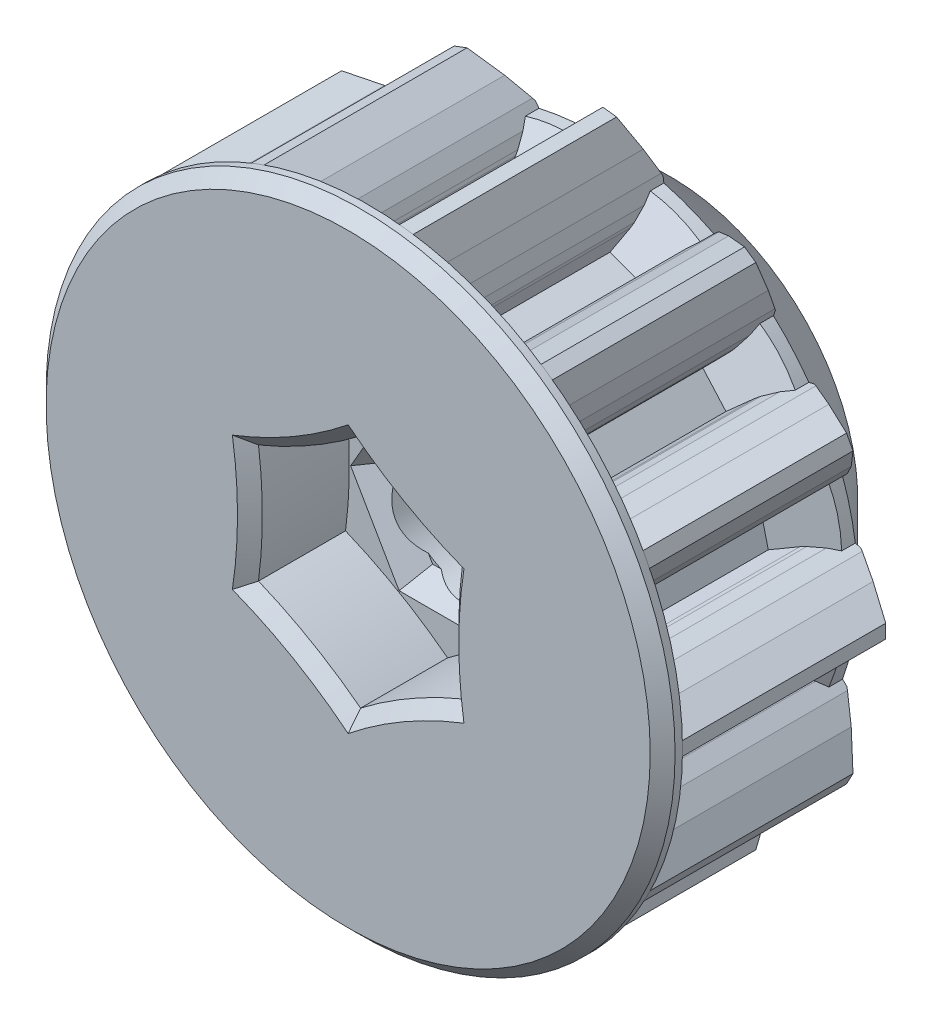
SolidWorks part; units mm, degrees
material "Custom Plastic"
ref_plane "Front Plane" through (0, 0, 0) normal (0, 0, 1) x (1, 0, 0)
ref_plane "Top Plane" through (0, 0, 0) normal (0, 1, 0) x (1, 0, 0)
ref_plane "Right Plane" through (0, 0, 0) normal (1, 0, 0) x (0, 0, -1)
sketch "Model" plane through (0, 0, 0) normal (0, 0, 1) x (1, 0, 0)
  line L0 (-12.322, -2.752) -> (-11.499, -1.837)
  line L1 (-11.499, -1.837) -> (-10.75, -1.243)
  line L2 (-10.75, -1.243) -> (-10.152, -0.913)
  line L3 (-10.152, -0.913) -> (-9.766, -0.777)
  line L4 (-9.766, -0.777) -> (-9.632, -0.751)
  line L5 (-9.632, -0.751) -> (-8.992, -0.701)
  line L6 (-8.992, -0.701) -> (-8.992, 0.701)
  line L7 (-8.992, 0.701) -> (-9.632, 0.751)
  line L8 (-9.632, 0.751) -> (-9.766, 0.777)
  line L9 (-9.766, 0.777) -> (-10.152, 0.913)
  line L10 (-10.152, 0.913) -> (-10.75, 1.243)
  line L11 (-10.75, 1.243) -> (-11.499, 1.837)
  line L12 (-11.499, 1.837) -> (-12.322, 2.752)
  line L13 (-12.322, 2.752) -> (-12.189, 3.29)
  line L14 (-12.189, 3.29) -> (-11.036, 3.717)
  line L15 (-11.036, 3.717) -> (-10.096, 3.895)
  line L16 (-10.096, 3.895) -> (-9.414, 3.91)
  line L17 (-9.414, 3.91) -> (-9.008, 3.851)
  line L18 (-9.008, 3.851) -> (-8.878, 3.811)
  line L19 (-8.878, 3.811) -> (-8.288, 3.558)
  line L20 (-8.288, 3.558) -> (-7.637, 4.8)
  line L21 (-7.637, 4.8) -> (-8.18, 5.141)
  line L22 (-8.18, 5.141) -> (-8.286, 5.226)
  line L23 (-8.286, 5.226) -> (-8.565, 5.527)
  line L24 (-8.565, 5.527) -> (-8.941, 6.096)
  line L25 (-8.941, 6.096) -> (-9.328, 6.971)
  line L26 (-9.328, 6.971) -> (-9.631, 8.163)
  line L27 (-9.631, 8.163) -> (-9.264, 8.577)
  line L28 (-9.264, 8.577) -> (-8.045, 8.42)
  line L29 (-8.045, 8.42) -> (-7.129, 8.141)
  line L30 (-7.129, 8.141) -> (-6.519, 7.837)
  line L31 (-6.519, 7.837) -> (-6.187, 7.596)
  line L32 (-6.187, 7.596) -> (-6.09, 7.501)
  line L33 (-6.09, 7.501) -> (-5.685, 7.002)
  line L34 (-5.685, 7.002) -> (-4.532, 7.799)
  line L35 (-4.532, 7.799) -> (-4.854, 8.354)
  line L36 (-4.854, 8.354) -> (-4.908, 8.478)
  line L37 (-4.908, 8.478) -> (-5.016, 8.874)
  line L38 (-5.016, 8.874) -> (-5.084, 9.553)
  line L39 (-5.084, 9.553) -> (-5.02, 10.508)
  line L40 (-5.02, 10.508) -> (-4.735, 11.704)
  line L41 (-4.735, 11.704) -> (-4.217, 11.9)
  line L42 (-4.217, 11.9) -> (-3.21, 11.194)
  line L43 (-3.21, 11.194) -> (-2.529, 10.522)
  line L44 (-2.529, 10.522) -> (-2.13, 9.968)
  line L45 (-2.13, 9.968) -> (-1.948, 9.601)
  line L46 (-1.948, 9.601) -> (-1.907, 9.471)
  line L47 (-1.907, 9.471) -> (-1.78, 8.842)
  line L48 (-1.78, 8.842) -> (-0.388, 9.011)
  line L49 (-0.388, 9.011) -> (-0.416, 9.652)
  line L50 (-0.416, 9.652) -> (-0.406, 9.788)
  line L51 (-0.406, 9.788) -> (-0.317, 10.189)
  line L52 (-0.317, 10.189) -> (-0.062, 10.821)
  line L53 (-0.062, 10.821) -> (0.438, 11.637)
  line L54 (0.438, 11.637) -> (1.246, 12.563)
  line L55 (1.246, 12.563) -> (1.796, 12.497)
  line L56 (1.796, 12.497) -> (2.36, 11.404)
  line L57 (2.36, 11.404) -> (2.65, 10.492)
  line L58 (2.65, 10.492) -> (2.746, 9.817)
  line L59 (2.746, 9.817) -> (2.737, 9.407)
  line L60 (2.737, 9.407) -> (2.713, 9.273)
  line L61 (2.713, 9.273) -> (2.533, 8.657)
  line L62 (2.533, 8.657) -> (3.845, 8.16)
  line L63 (3.845, 8.16) -> (4.118, 8.74)
  line L64 (4.118, 8.74) -> (4.189, 8.856)
  line L65 (4.189, 8.856) -> (4.454, 9.169)
  line L66 (4.454, 9.169) -> (4.974, 9.611)
  line L67 (4.974, 9.611) -> (5.796, 10.101)
  line L68 (5.796, 10.101) -> (6.942, 10.545)
  line L69 (6.942, 10.545) -> (7.398, 10.23)
  line L70 (7.398, 10.23) -> (7.389, 9.001)
  line L71 (7.389, 9.001) -> (7.222, 8.059)
  line L72 (7.222, 8.059) -> (6.994, 7.416)
  line L73 (6.994, 7.416) -> (6.795, 7.057)
  line L74 (6.795, 7.057) -> (6.712, 6.949)
  line L75 (6.712, 6.949) -> (6.266, 6.487)
  line L76 (6.266, 6.487) -> (7.196, 5.438)
  line L77 (7.196, 5.438) -> (7.708, 5.825)
  line L78 (7.708, 5.825) -> (7.825, 5.895)
  line L79 (7.825, 5.895) -> (8.205, 6.049)
  line L80 (8.205, 6.049) -> (8.871, 6.198)
  line L81 (8.871, 6.198) -> (9.826, 6.25)
  line L82 (9.826, 6.25) -> (11.047, 6.111)
  line L83 (11.047, 6.111) -> (11.305, 5.62)
  line L84 (11.305, 5.62) -> (10.726, 4.536)
  line L85 (10.726, 4.536) -> (10.14, 3.779)
  line L86 (10.14, 3.779) -> (9.639, 3.316)
  line L87 (9.639, 3.316) -> (9.296, 3.091)
  line L88 (9.296, 3.091) -> (9.173, 3.034)
  line L89 (9.173, 3.034) -> (8.563, 2.832)
  line L90 (8.563, 2.832) -> (8.899, 1.471)
  line L91 (8.899, 1.471) -> (9.532, 1.576)
  line L92 (9.532, 1.576) -> (9.668, 1.583)
  line L93 (9.668, 1.583) -> (10.076, 1.543)
  line L94 (10.076, 1.543) -> (10.735, 1.366)
  line L95 (10.735, 1.366) -> (11.605, 0.968)
  line L96 (11.605, 0.968) -> (12.622, 0.277)
  line L97 (12.622, 0.277) -> (12.622, -0.277)
  line L98 (12.622, -0.277) -> (11.605, -0.968)
  line L99 (11.605, -0.968) -> (10.735, -1.366)
  line L100 (10.735, -1.366) -> (10.076, -1.543)
  line L101 (10.076, -1.543) -> (9.668, -1.583)
  line L102 (9.668, -1.583) -> (9.532, -1.576)
  line L103 (9.532, -1.576) -> (8.899, -1.471)
  line L104 (8.899, -1.471) -> (8.563, -2.832)
  line L105 (8.563, -2.832) -> (9.173, -3.034)
  line L106 (9.173, -3.034) -> (9.296, -3.091)
  line L107 (9.296, -3.091) -> (9.639, -3.316)
  line L108 (9.639, -3.316) -> (10.14, -3.779)
  line L109 (10.14, -3.779) -> (10.726, -4.536)
  line L110 (10.726, -4.536) -> (11.305, -5.62)
  line L111 (11.305, -5.62) -> (11.047, -6.111)
  line L112 (11.047, -6.111) -> (9.826, -6.25)
  line L113 (9.826, -6.25) -> (8.871, -6.198)
  line L114 (8.871, -6.198) -> (8.205, -6.049)
  line L115 (8.205, -6.049) -> (7.825, -5.895)
  line L116 (7.825, -5.895) -> (7.708, -5.825)
  line L117 (7.708, -5.825) -> (7.196, -5.438)
  line L118 (7.196, -5.438) -> (6.266, -6.487)
  line L119 (6.266, -6.487) -> (6.712, -6.949)
  line L120 (6.712, -6.949) -> (6.795, -7.057)
  line L121 (6.795, -7.057) -> (6.994, -7.416)
  line L122 (6.994, -7.416) -> (7.222, -8.059)
  line L123 (7.222, -8.059) -> (7.389, -9.001)
  line L124 (7.389, -9.001) -> (7.398, -10.23)
  line L125 (7.398, -10.23) -> (6.942, -10.545)
  line L126 (6.942, -10.545) -> (5.796, -10.101)
  line L127 (5.796, -10.101) -> (4.974, -9.611)
  line L128 (4.974, -9.611) -> (4.454, -9.169)
  line L129 (4.454, -9.169) -> (4.189, -8.856)
  line L130 (4.189, -8.856) -> (4.118, -8.74)
  line L131 (4.118, -8.74) -> (3.845, -8.16)
  line L132 (3.845, -8.16) -> (2.533, -8.657)
  line L133 (2.533, -8.657) -> (2.713, -9.273)
  line L134 (2.713, -9.273) -> (2.737, -9.407)
  line L135 (2.737, -9.407) -> (2.746, -9.817)
  line L136 (2.746, -9.817) -> (2.65, -10.492)
  line L137 (2.65, -10.492) -> (2.36, -11.404)
  line L138 (2.36, -11.404) -> (1.796, -12.497)
  line L139 (1.796, -12.497) -> (1.246, -12.563)
  line L140 (1.246, -12.563) -> (0.438, -11.637)
  line L141 (0.438, -11.637) -> (-0.062, -10.821)
  line L142 (-0.062, -10.821) -> (-0.317, -10.189)
  line L143 (-0.317, -10.189) -> (-0.406, -9.788)
  line L144 (-0.406, -9.788) -> (-0.416, -9.652)
  line L145 (-0.416, -9.652) -> (-0.388, -9.011)
  line L146 (-0.388, -9.011) -> (-1.78, -8.842)
  line L147 (-1.78, -8.842) -> (-1.907, -9.471)
  line L148 (-1.907, -9.471) -> (-1.948, -9.601)
  line L149 (-1.948, -9.601) -> (-2.13, -9.968)
  line L150 (-2.13, -9.968) -> (-2.529, -10.522)
  line L151 (-2.529, -10.522) -> (-3.21, -11.194)
  line L152 (-3.21, -11.194) -> (-4.217, -11.9)
  line L153 (-4.217, -11.9) -> (-4.735, -11.704)
  line L154 (-4.735, -11.704) -> (-5.02, -10.508)
  line L155 (-5.02, -10.508) -> (-5.084, -9.553)
  line L156 (-5.084, -9.553) -> (-5.016, -8.874)
  line L157 (-5.016, -8.874) -> (-4.908, -8.478)
  line L158 (-4.908, -8.478) -> (-4.854, -8.354)
  line L159 (-4.854, -8.354) -> (-4.532, -7.799)
  line L160 (-4.532, -7.799) -> (-5.685, -7.002)
  line L161 (-5.685, -7.002) -> (-6.09, -7.501)
  line L162 (-6.09, -7.501) -> (-6.187, -7.596)
  line L163 (-6.187, -7.596) -> (-6.519, -7.837)
  line L164 (-6.519, -7.837) -> (-7.129, -8.141)
  line L165 (-7.129, -8.141) -> (-8.045, -8.42)
  line L166 (-8.045, -8.42) -> (-9.264, -8.577)
  line L167 (-9.264, -8.577) -> (-9.631, -8.163)
  line L168 (-9.631, -8.163) -> (-9.328, -6.971)
  line L169 (-9.328, -6.971) -> (-8.941, -6.096)
  line L170 (-8.941, -6.096) -> (-8.565, -5.527)
  line L171 (-8.565, -5.527) -> (-8.286, -5.226)
  line L172 (-8.286, -5.226) -> (-8.18, -5.141)
  line L173 (-8.18, -5.141) -> (-7.637, -4.8)
  line L174 (-7.637, -4.8) -> (-8.288, -3.558)
  line L175 (-8.288, -3.558) -> (-8.878, -3.811)
  line L176 (-8.878, -3.811) -> (-9.008, -3.851)
  line L177 (-9.008, -3.851) -> (-9.414, -3.91)
  line L178 (-9.414, -3.91) -> (-10.096, -3.895)
  line L179 (-10.096, -3.895) -> (-11.036, -3.717)
  line L180 (-11.036, -3.717) -> (-12.189, -3.29)
  line L181 (-12.189, -3.29) -> (-12.322, -2.752)
  line L182 (0, 0) -> (12.622, 0) construction
  line L183 (8.899, 1.471) -> (8.899, -1.471) construction
  line L184 (9.532, 1.576) -> (9.532, -1.576) construction
  line L185 (9.668, 1.583) -> (9.668, -1.583) construction
  line L186 (10.076, 1.543) -> (10.076, -1.543) construction
  line L187 (10.735, 1.366) -> (10.735, -1.366) construction
  line L188 (11.605, 0.968) -> (11.605, -0.968) construction
  circle A0 centre (0, 0) radius 1.5 construction
  dimension "D1" = 3
  dimension "D2" = 12.622
  dimension "D3" = 0.554
  dimension "D4" = 2.942
  dimension "D5" = 3.152
  dimension "D6" = 3.166
  dimension "D7" = 3.086
  dimension "D8" = 2.732
  dimension "D9" = 1.936
  dimension "D10" = 8.899
  dimension "D11" = 9.532
  dimension "D12" = 9.668
  dimension "D13" = 10.076
  dimension "D14" = 10.735
  dimension "D15" = 11.605
extrude "Boss-Extrude1" add sketch "Model" along normal blind 10
sketch "Sketch1" plane through (0, 0, 0) normal (0, 0, -1) x (-1, 0, 0)
  circle A0 centre (0, 0) radius 10.5
  dimension "D1" = 21
extrude "Boss-Extrude2" add sketch "Sketch1" along normal blind 3
sketch "Sketch6" plane through (0, 0, 10) normal (0, 0, 1) x (1, 0, 0)
  circle A0 centre (0, 0) radius 12.65
  dimension "D1" = 25.3
extrude "Boss-Extrude3" add sketch "Sketch6" against normal blind 0.8
chamfer "Chamfer1" distance 2 distance2 2 13 edges at (8.731, -2.1515, 0) (6.731, -5.9625, 0) (3.189, -8.4085, 0) (-1.084, -8.9265, 0) (-5.1085, -7.4005, 0) (-7.9625, -4.179, 0) (-8.992, 0, 0) (-7.9625, 4.179, 0) (-5.1085, 7.4005, 0) (-1.084, 8.9265, 0) (3.189, 8.4085, 0) (6.731, 5.9625, 0) (8.731, 2.1515, 0)
sketch "Sketch2" plane through (0, 0, 10) normal (0, 0, 1) x (1, 0, 0)
  circle A0 centre (0, 0) radius 3.05
  dimension "D1" = 6.1
extrude "Cut-Extrude1" cut sketch "Sketch2" against normal through all
sketch "Sketch3" plane through (0, 0, -3) normal (0, 0, -1) x (-1, 0, 0)
  circle A0 centre (0, 0) radius 5.05
  dimension "D1" = 10.1
extrude "Cut-Extrude2" cut sketch "Sketch3" against normal blind 4
sketch "Sketch4" plane through (0, 0, 10) normal (0, 0, 1) x (1, 0, 0)
  line L1 (3.9, 0) -> (1.95, 3.3775)
  line L2 (1.95, 3.3775) -> (-1.95, 3.3775)
  line L3 (-1.95, 3.3775) -> (-3.9, 0)
  line L4 (-3.9, 0) -> (-1.95, -3.3775)
  line L5 (-1.95, -3.3775) -> (1.95, -3.3775)
  line L6 (1.95, -3.3775) -> (3.9, 0)
  circle A0 centre (0, 0) radius 3.9 construction
  circle A1 centre (0, 0) radius 3.3775 construction
  dimension "D1" = 7.8
extrude "Cut-Extrude3" cut sketch "Sketch4" against normal offset from surface (5 mm away) 4 up to face at (-5.05, 0, 1)
sketch "Sketch5" plane through (0, 0, 10) normal (0, 0, 1) x (1, 0, 0)
  line L0 (0, 0) -> (11, 19.0526) construction
  line L1 (-3.95, 2.2805) -> (-3.95, -2.2805) construction
  line L2 (-3.95, -2.2805) -> (0, -4.5611) construction
  line L3 (0, -4.5611) -> (3.95, -2.2805) construction
  line L4 (3.95, -2.2805) -> (3.95, 2.2805) construction
  line L5 (3.95, 2.2805) -> (0, 4.5611) construction
  line L6 (0, 4.5611) -> (-3.95, 2.2805) construction
  line L7 (0, 0) -> (0, 6.6728) construction
  line L8 (0, 0) -> (8.0758, 4.6625) construction
  circle A0 centre (0, 0) radius 3.95 construction
  arc A1 (0, 4.7416) -> (4.1064, 2.3708) centre (11, 19.0526) ccw
  arc A2 (4.1064, 2.3708) -> (4.1064, -2.3708) centre (22, 0) ccw
  arc A3 (4.1064, -2.3708) -> (0, -4.7416) centre (11, -19.0526) ccw
  arc A4 (0, -4.7416) -> (-4.1064, -2.3708) centre (-11, -19.0526) ccw
  arc A5 (-4.1064, -2.3708) -> (-4.1064, 2.3708) centre (-22, 0) ccw
  arc A6 (-4.1064, 2.3708) -> (0, 4.7416) centre (-11, 19.0526) ccw
  point P35 (0, 0)
  dimension "D1" = 7.9
  dimension "D3" = 22
  dimension "D2" = 6
extrude "Cut-Extrude4" cut sketch "Sketch5" against normal blind 4
chamfer "Chamfer4" distance 3 angle 45 1 edges at (-10.5, 0, -3)
chamfer "Chamfer5" distance 2 distance2 1 13 edges at (1.521, 12.53, 0) (7.17, 10.3875, 0) (11.176, 5.8655, 0) (12.622, 0, 0) (11.176, -5.8655, 0) (7.17, -10.3875, 0) (1.521, -12.53, 0) (-4.476, -11.802, 0) (-9.4475, -8.37, 0) (-12.2555, -3.021, 0) (-12.2555, 3.021, 0) (-9.4475, 8.37, 0) (-4.476, 11.802, 0) first distance on face at (1.3684, 11.27, 0) first distance on face at (6.4491, 9.3433, 0) first distance on face at (10.0525, 5.2757, 0) first distance on face at (11.3528, 0, 0) first distance on face at (10.0525, -5.2757, 0) first distance on face at (6.4491, -9.3433, 0) first distance on face at (1.3684, -11.27, 0) first distance on face at (-4.0257, -10.6152, 0) first distance on face at (-8.4976, -7.5283, 0) first distance on face at (-11.0229, -2.7169, 0) first distance on face at (-11.0229, 2.7169, 0) first distance on face at (-8.4976, 7.5283, 0) first distance on face at (-4.0257, 10.6152, 0)
chamfer "Chamfer6" distance 0.5 angle 45 7 edges at (12.65, 0, 10) (3.95, 0, 10) (1.975, 3.4208, 10) (-1.975, 3.4208, 10) (-3.95, 0, 10) (-1.975, -3.4208, 10) (1.975, -3.4208, 10)
chamfer "Chamfer7" distance 1 angle 60 13 edges at (-7.9625, -4.179, 9.2) (-5.1085, -7.4005, 9.2) (-1.084, -8.9265, 9.2) (3.189, -8.4085, 9.2) (6.731, -5.9625, 9.2) (8.731, -2.1515, 9.2) (8.731, 2.1515, 9.2) (6.731, 5.9625, 9.2) (3.189, 8.4085, 9.2) (-1.084, 8.9265, 9.2) (-5.1085, 7.4005, 9.2) (-7.9625, 4.179, 9.2) (-8.992, 0, 9.2) first distance on face at (-7.9625, -4.179, 5.6) first distance on face at (-5.1085, -7.4005, 5.6) first distance on face at (-1.084, -8.9265, 5.6) first distance on face at (3.189, -8.4085, 5.6) first distance on face at (6.731, -5.9625, 5.6) first distance on face at (8.731, -2.1515, 5.6) first distance on face at (8.731, 2.1515, 5.6) first distance on face at (6.731, 5.9625, 5.6) first distance on face at (3.189, 8.4085, 5.6) first distance on face at (-1.084, 8.9265, 5.6) first distance on face at (-5.1085, 7.4005, 5.6) first distance on face at (-7.9625, 4.179, 5.6) first distance on face at (-8.992, 0, 5.6)
chamfer "Chamfer8" distance 1 distance2 0.6 6 edges at (0, -3.3775, 5) (2.925, -1.6887, 5) (2.925, 1.6887, 5) (0, 3.3775, 5) (-2.925, 1.6887, 5) (-2.925, -1.6887, 5) first distance on face at (0, -3.3775, 5.5) first distance on face at (2.925, -1.6887, 5.5) first distance on face at (2.925, 1.6887, 5.5) first distance on face at (0, 3.3775, 5.5) first distance on face at (-2.925, 1.6887, 5.5) first distance on face at (-2.925, -1.6887, 5.5)
chamfer "Chamfer9" distance 0.5 angle 45 1 edges at (-5.05, 0, -3)
